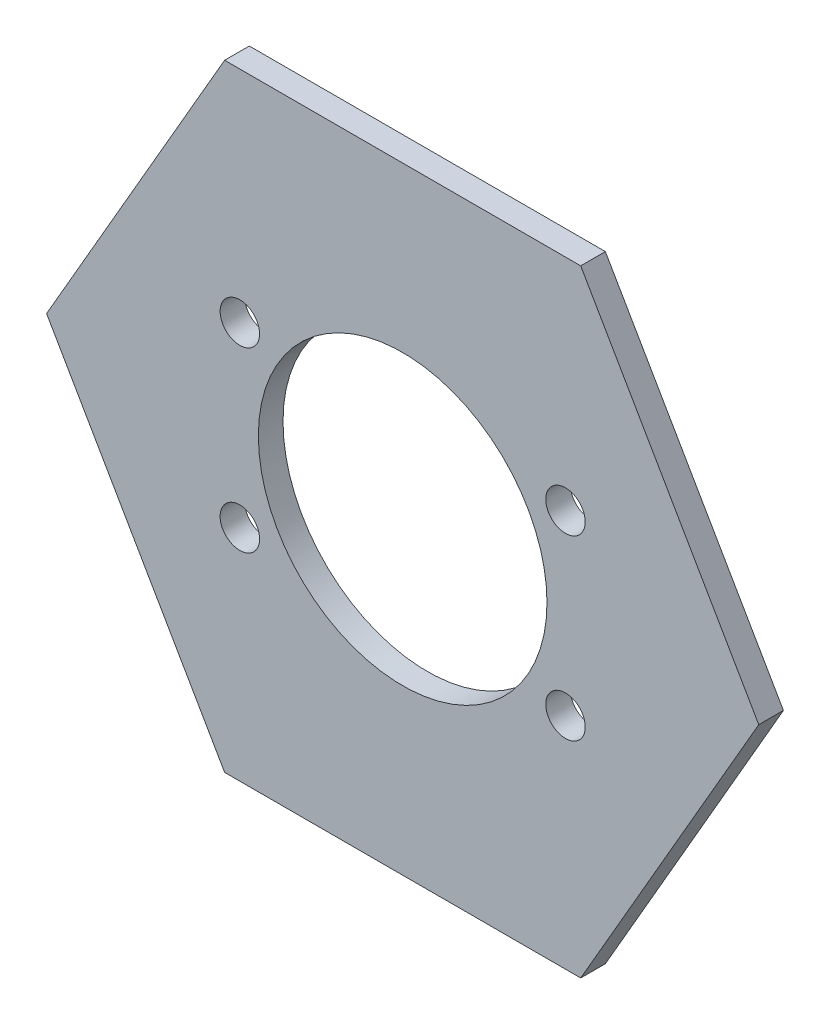
SolidWorks part; units mm, degrees
ref_plane "Front Plane" through (0, 0, 0) normal (0, 0, 1) x (1, 0, 0)
ref_plane "Top Plane" through (0, 0, 0) normal (0, 1, 0) x (1, 0, 0)
ref_plane "Right Plane" through (0, 0, 0) normal (1, 0, 0) x (0, 0, -1)
sketch "Sketch1" plane through (0, 0, 0) normal (0, 0, 1) x (1, 0, 0)
  line L0 (0, 0) -> (0, -25) construction
  line L1 (-5, -17.5) -> (5, -17.5) construction
  line L2 (-14.4338, 25) -> (14.4338, 25)
  line L3 (-5, -19) -> (5, -19) construction
  line L4 (-5, -19) -> (-5, -24) construction
  line L5 (-5, -24) -> (5, -24) construction
  line L6 (5, -19) -> (5, -24) construction
  line L7 (14.4338, 25) -> (28.8675, 0)
  line L8 (28.8675, 0) -> (14.4338, -25)
  line L9 (14.4338, -25) -> (-14.4338, -25)
  line L10 (-14.4338, -25) -> (-28.8675, 0)
  line L11 (-28.8675, 0) -> (-14.4338, 25)
  circle A0 centre (0, 0) radius 8 construction
  circle A1 centre (0, 0) radius 11.7
  circle A2 centre (0, 0) radius 11.2 construction
  circle A3 centre (0, 0) radius 11.2 construction
  circle A6 centre (-13.2, -7.2) radius 1.6
  circle A7 centre (-13.2, 7.2) radius 1.6
  circle A8 centre (13.2, 7.2) radius 1.6
  circle A9 centre (13.2, -7.2) radius 1.6
  circle A10 centre (0, 0) radius 25 construction
  circle A11 centre (-13.2, -7.2) radius 1.6 construction
  circle A12 centre (-13.2, 7.2) radius 1.6 construction
  circle A13 centre (13.2, 7.2) radius 1.6 construction
  circle A14 centre (13.2, -7.2) radius 1.6 construction
  dimension "D2" = 50
  dimension "D1" = 0.5
  dimension "D3" = 5
  dimension "D4" = 10
  dimension "D5" = 1
extrude "Boss-Extrude1" add sketch "Sketch1" along normal blind 2
